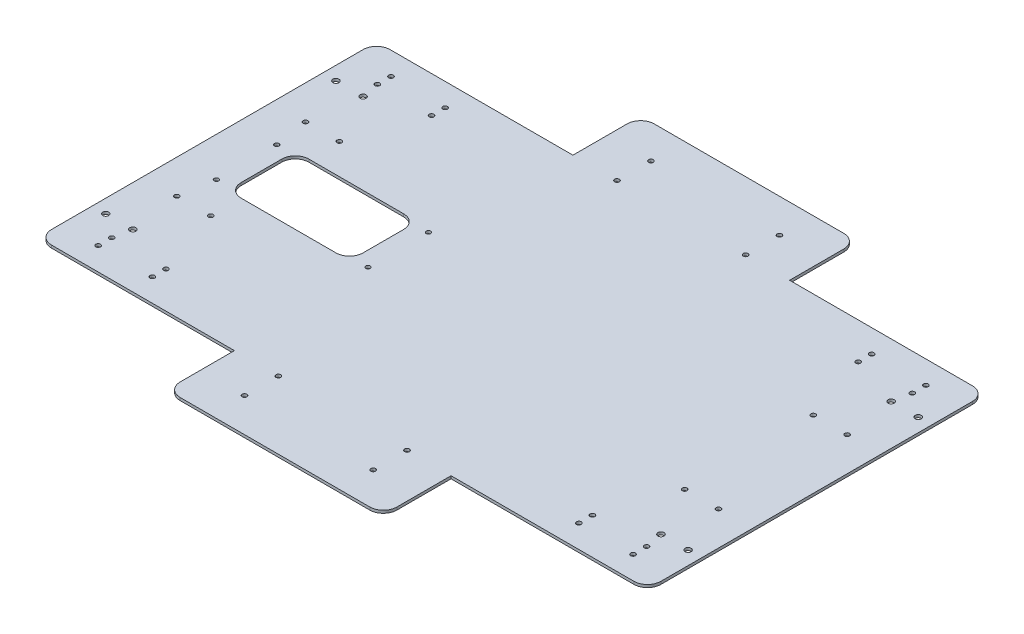
SolidWorks part; units mm, degrees
material "1060 Alloy"
ref_plane "Front Plane" through (0, 0, 0) normal (0, 0, 1) x (1, 0, 0)
ref_plane "Top Plane" through (0, 0, 0) normal (0, 1, 0) x (1, 0, 0)
ref_plane "Right Plane" through (0, 0, 0) normal (1, 0, 0) x (0, 0, -1)
sketch "Sketch5" plane through (0, 0, 0) normal (0, 1, 0) x (1, 0, 0)
  line L1 (0, 0) -> (450, 0)
  line L2 (0, 0) -> (0, 350)
  line L3 (0, 350) -> (450, 350)
  line L4 (450, 0) -> (450, 350)
  dimension "D1" = 450
  dimension "D2" = 350
extrude "Boss-Extrude1" add sketch "Sketch5" along normal blind 2 contours L2 L3 L4 L1
fillet "Fillet1" radius 10 4 edges at (0, 1, -350) (450, 1, -350) (450, 1, 0) (0, 1, 0)
sketch "Sketch6" plane through (0, 2, 0) normal (0, 1, 0) x (1, 0, 0)
  line L0 (85, 0) -> (85, 350) construction
  line L1 (130, 190) -> (130, 160)
  line L2 (120, 200) -> (50, 200)
  line L3 (40, 190) -> (40, 160)
  line L4 (120, 150) -> (50, 150)
  line L5 (10, 350) -> (440, 350) construction
  line L6 (40, 175) -> (130, 175) construction
  line L7 (85, 200) -> (85, 150) construction
  line L9 (0, 10) -> (0, 340) construction
  line L10 (10, 0) -> (440, 0) construction
  arc A0 (50, 200) -> (40, 190) centre (50, 190) ccw
  arc A1 (40, 160) -> (50, 150) centre (50, 160) ccw
  arc A2 (130, 160) -> (120, 150) centre (120, 160) cw
  arc A3 (130, 190) -> (120, 200) centre (120, 190) ccw
  point P20 (85, 175)
  point P21 (85, 175)
  dimension "D1" = 10
  dimension "D2" = 50
  dimension "D3" = 90
  dimension "D4" = 85
extrude "Cut-Extrude1" cut sketch "Sketch6" against normal through all
sketch "Sketch7" plane through (0, 2, 0) normal (0, 1, 0) x (1, 0, 0)
  line L0 (10, 0) -> (440, 0) construction
  line L1 (0, 10) -> (0, 340) construction
  line L2 (135, 30) -> (135, 10) construction
  line L3 (10, 90) -> (30, 90) construction
  line L4 (225, 350) -> (225, 0) construction
  line L5 (10, 350) -> (440, 350) construction
  line L6 (0, 175) -> (450, 175) construction
  line L7 (450, 10) -> (450, 340) construction
  point P0 (135, 10)
  point P1 (135, 30)
  point P2 (10, 90)
  point P3 (30, 90)
  point P20 (315, 10)
  point P21 (315, 30)
  point P22 (420, 90)
  point P23 (440, 90)
  point P24 (440, 260)
  point P25 (420, 260)
  point P26 (315, 340)
  point P27 (315, 320)
  point P28 (135, 340)
  point P29 (135, 320)
  point P30 (30, 260)
  point P31 (10, 260)
  dimension "D1" = 10
  dimension "D2" = 20
  dimension "D3" = 10
  dimension "D4" = 20
  dimension "D5" = 135
  dimension "D6" = 90
hole_wizard "M4 Clearance Hole1" positions "Sketch7" profile "Sketch8" hole size "M4" standard "ANSI Metric" end condition through all
sketch "Sketch8" plane through (135, 2, -10) normal (1, 0, 0) x (0, 0, 1)
  line L0 (0, 0) -> (0, 2)
  line L1 (0, 2) -> (2.25, 2)
  line L2 (2.25, 2) -> (2.25, 0)
  line L5 (2.25, 0) -> (0, 0)
  line L11 (0, -6.35) -> (0, 107.95) construction
  dimension "Thru Hole Dia." = 4.5
  dimension "Thru Hole Depth" = 2
sketch "Sketch13" plane through (0, 2, 0) normal (0, 1, 0) x (1, 0, 0)
  line L0 (0, 175) -> (450, 175) construction
  line L1 (0, 10) -> (0, 340) construction
  line L2 (450, 10) -> (450, 340) construction
  line L3 (225, 175) -> (225, 227.8107) construction
  line L4 (25, 222.5) -> (50, 222.5) construction
  line L5 (25, 222.5) -> (25, 127.5) construction
  line L6 (177.5, 325.0262) -> (272.5, 325.0262) construction
  line L7 (177.5, 325.0262) -> (177.5, 300.0262) construction
  circle A0 centre (272.5, 49.9738) radius 1.75
  circle A1 centre (272.5, 24.9738) radius 1.75
  circle A2 centre (177.5, 49.9738) radius 1.75
  circle A3 centre (177.5, 24.9738) radius 1.75
  arc A16 (272.5, 301.6762) -> (272.5, 298.3762) centre (272.5, 300.0262) ccw construction
  arc A17 (272.5, 298.3762) -> (272.5, 301.6762) centre (272.5, 300.0262) ccw construction
  arc A18 (272.5, 326.6762) -> (272.5, 323.3762) centre (272.5, 325.0262) ccw construction
  arc A19 (272.5, 323.3762) -> (272.5, 326.6762) centre (272.5, 325.0262) ccw construction
  arc A20 (177.5, 301.6762) -> (177.5, 298.3762) centre (177.5, 300.0262) ccw construction
  arc A21 (177.5, 298.3762) -> (177.5, 301.6762) centre (177.5, 300.0262) ccw construction
  arc A22 (177.5, 326.6762) -> (177.5, 323.3762) centre (177.5, 325.0262) ccw construction
  arc A23 (177.5, 323.3762) -> (177.5, 326.6762) centre (177.5, 325.0262) ccw construction
  arc A48 (272.5, 301.6762) -> (272.5, 298.3762) centre (272.5, 300.0262) ccw construction
  arc A49 (272.5, 298.3762) -> (272.5, 301.6762) centre (272.5, 300.0262) ccw construction
  arc A50 (272.5, 326.6762) -> (272.5, 323.3762) centre (272.5, 325.0262) ccw construction
  arc A51 (272.5, 323.3762) -> (272.5, 326.6762) centre (272.5, 325.0262) ccw construction
  arc A52 (177.5, 301.6762) -> (177.5, 298.3762) centre (177.5, 300.0262) ccw construction
  arc A53 (177.5, 298.3762) -> (177.5, 301.6762) centre (177.5, 300.0262) ccw construction
  arc A54 (177.5, 326.6762) -> (177.5, 323.3762) centre (177.5, 325.0262) ccw construction
  arc A55 (177.5, 323.3762) -> (177.5, 326.6762) centre (177.5, 325.0262) ccw construction
  circle A64 centre (25, 222.5) radius 1.75
  circle A65 centre (50, 222.5) radius 1.75
  circle A66 centre (50, 127.5) radius 1.75
  circle A67 centre (25, 127.5) radius 1.75
  circle A68 centre (177.5, 325.0262) radius 1.75
  circle A69 centre (272.5, 325.0262) radius 1.75
  circle A70 centre (272.5, 300.0262) radius 1.75
  circle A71 centre (177.5, 300.0262) radius 1.75
  circle A72 centre (425, 127.5) radius 1.75
  circle A73 centre (400, 127.5) radius 1.75
  circle A74 centre (400, 222.5) radius 1.75
  circle A75 centre (425, 222.5) radius 1.75
  point P9 (25, 175)
  dimension "D1" = 3.5
  dimension "D2" = 2
  dimension "D6" = 3.5
  dimension "D4" = 25
  dimension "D5" = 95
  dimension "D9" = 95
  dimension "D10" = 25
  dimension "D11" = 25
  dimension "D3" = 2
  dimension "D7" = 2
  dimension "D8" = 2
extrude "Cut-Extrude2" cut sketch "Sketch13" against normal through all
sketch "Sketch14" plane through (0, 2, 0) normal (0, 1, 0) x (1, 0, 0)
  line L0 (27.5, 76.9004) -> (67.5, 76.9004) construction
  line L1 (27.5, 76.9004) -> (27.5, 66.9004) construction
  line L2 (0, 175) -> (450, 175) construction
  line L3 (0, 10) -> (0, 340) construction
  line L4 (450, 10) -> (450, 340) construction
  line L5 (225, 175) -> (225, 224.2921) construction
  line L6 (10, 0) -> (440, 0) construction
  circle A16 centre (27.5, 76.9004) radius 1.75
  circle A17 centre (67.5, 76.9004) radius 1.75
  circle A18 centre (67.5, 66.9004) radius 1.75
  circle A19 centre (27.5, 66.9004) radius 1.75
  circle A20 centre (67.5, 283.0996) radius 1.75
  circle A21 centre (67.5, 273.0996) radius 1.75
  circle A22 centre (27.5, 283.0996) radius 1.75
  circle A23 centre (27.5, 273.0996) radius 1.75
  circle A24 centre (382.5, 273.0996) radius 1.75
  circle A25 centre (382.5, 283.0996) radius 1.75
  circle A26 centre (422.5, 283.0996) radius 1.75
  circle A27 centre (422.5, 273.0996) radius 1.75
  circle A28 centre (422.5, 66.9004) radius 1.75
  circle A29 centre (382.5, 66.9004) radius 1.75
  circle A30 centre (382.5, 76.9004) radius 1.75
  circle A31 centre (422.5, 76.9004) radius 1.75
  dimension "D1" = 3.5
  dimension "D4" = 40
  dimension "D5" = 10
  dimension "D6" = 27.5
  dimension "D7" = 76.9004
  dimension "D2" = 2
  dimension "D3" = 2
extrude "Cut-Extrude3" cut sketch "Sketch14" against normal through all
sketch "Sketch15" plane through (0, 2, 0) normal (0, 1, 0) x (1, 0, 0)
  line L0 (0, 175) -> (450, 175) construction
  line L1 (0, 350) -> (145, 350)
  line L2 (0, 350) -> (0, 300)
  line L3 (0, 300) -> (145, 300)
  line L4 (145, 350) -> (145, 300)
  line L5 (0, 350) -> (145, 300) construction
  line L6 (0, 300) -> (145, 350) construction
  line L7 (0, 10) -> (0, 340) construction
  line L8 (450, 10) -> (450, 340) construction
  line L9 (225, 175) -> (225, 236.2931) construction
  line L10 (0, 50) -> (145, 0) construction
  line L11 (0, 0) -> (145, 50) construction
  line L12 (145, 0) -> (145, 50)
  line L13 (0, 50) -> (145, 50)
  line L14 (0, 0) -> (0, 50)
  line L15 (0, 0) -> (145, 0)
  line L16 (450, 0) -> (305, 50) construction
  line L17 (450, 50) -> (305, 0) construction
  line L18 (450, 0) -> (305, 0)
  line L19 (450, 0) -> (450, 50)
  line L20 (450, 50) -> (305, 50)
  line L21 (305, 0) -> (305, 50)
  line L22 (450, 300) -> (305, 350) construction
  line L23 (450, 350) -> (305, 300) construction
  line L24 (305, 350) -> (305, 300)
  line L25 (450, 300) -> (305, 300)
  line L26 (450, 350) -> (450, 300)
  line L27 (450, 350) -> (305, 350)
  line L28 (10, 350) -> (440, 350) construction
  point P4 (72.5, 325)
  point P17 (72.5, 25)
  point P22 (377.5, 25)
  point P27 (377.5, 325)
  dimension "D1" = 50
  dimension "D2" = 145
extrude "Cut-Extrude4" cut sketch "Sketch15" against normal through all
fillet "Fillet2" radius 10 8 edges at (0, 1, -50) (145, 1, 0) (305, 1, 0) (450, 1, -50) (450, 1, -300) (305, 1, -350) (145, 1, -350) (0, 1, -300)
sketch "Sketch16" plane through (0, 2, 0) normal (0, 1, 0) x (1, 0, 0)
  line L0 (29, 197.3) -> (29, 152.7) construction
  line L1 (40, 175) -> (130, 175) construction
  line L2 (40, 190) -> (40, 160) construction
  line L3 (130, 160) -> (130, 190) construction
  line L4 (85, 175) -> (85, 183.1804) construction
  circle A0 centre (29, 197.3) radius 1.65
  circle A1 centre (29, 152.7) radius 1.65
  circle A2 centre (141, 152.7) radius 1.65
  circle A3 centre (141, 197.3) radius 1.65
  point P8 (29, 175)
  dimension "D2" = 3.3
  dimension "D1" = 44.6
  dimension "D3" = 56
extrude "Cut-Extrude5" cut sketch "Sketch16" against normal through all
